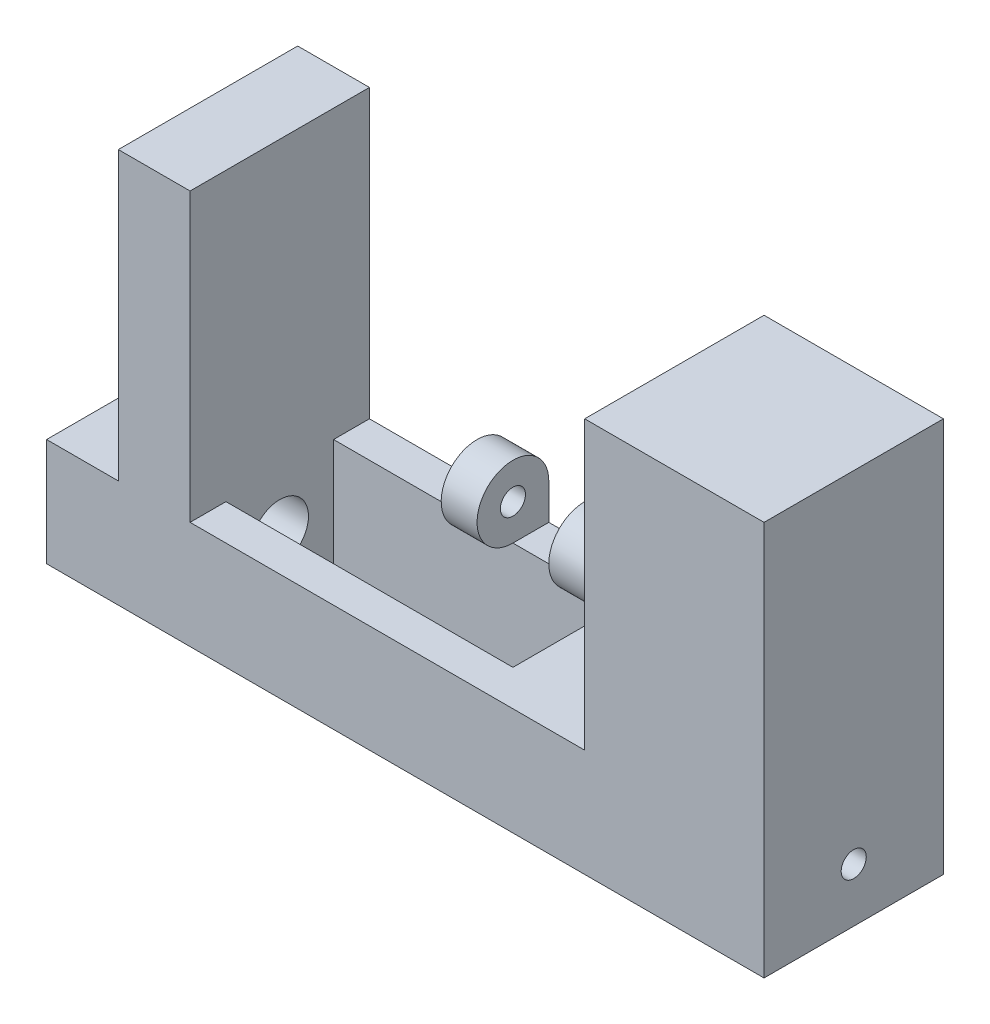
SolidWorks part; units mm, degrees
ref_plane "Front Plane" through (0, 0, 0) normal (0, 0, 1) x (1, 0, 0)
ref_plane "Top Plane" through (0, 0, 0) normal (0, 1, 0) x (1, 0, 0)
ref_plane "Right Plane" through (0, 0, 0) normal (1, 0, 0) x (0, 0, -1)
sketch "Sketch2" plane through (0, 0, 0) normal (0, 1, 0) x (1, 0, 0)
  line L1 (-20, -7.5) -> (20, -7.5)
  line L2 (-20, -7.5) -> (-20, 7.5)
  line L3 (-20, 7.5) -> (20, 7.5)
  line L4 (20, -7.5) -> (20, 7.5)
  line L5 (-20, -7.5) -> (20, 7.5) construction
  line L6 (-20, 7.5) -> (20, -7.5) construction
  line L7 (-40, -12.5) -> (60, -12.5)
  line L8 (-40, -12.5) -> (-40, 12.5)
  line L9 (-40, 12.5) -> (60, 12.5)
  line L10 (60, -12.5) -> (60, 12.5)
  point P0 (0, 0)
  point P10 (-40, 0)
  dimension "D1" = 15
  dimension "D2" = 25
  dimension "D3" = 20
  dimension "D4" = 40
  dimension "D5" = 40
extrude "Boss-Extrude1" add sketch "Sketch2" along normal blind 15
sketch "Sketch3" plane through (60, 0, 0) normal (1, 0, 0) x (0, 0, -1)
  line L0 (0, 0) -> (0, 7.5) construction
  line L1 (-12.5, 0) -> (12.5, 0) construction
  circle A0 centre (0, 7.5) radius 1.75
  dimension "D1" = 3.5
  dimension "D2" = 7.5
extrude "Cut-Extrude1" cut sketch "Sketch3" against normal up to next
sketch "Sketch4" plane through (-40, 0, 0) normal (-1, 0, 0) x (0, 0, 1)
  circle A0 centre (0, 7.5) radius 4
  point P2 (-1.0899, 7.4204)
  dimension "D2" = 8
  dimension "D1" = 7.5
extrude "Cut-Extrude2" cut sketch "Sketch4" against normal up to next
sketch "Sketch7" plane through (0, 15, 0) normal (0, 1, 0) x (1, 0, 0)
  line L0 (-40, 12.5) -> (-40, -12.5) construction
  point P0 (-35, 0)
  point P5 (0, 0)
  dimension "D1" = 5
hole_wizard "Ø3.2 (3.2) Diameter Hole1" positions "Sketch7" profile "Sketch6" hole size "Ø3.2" standard "ANSI Metric" end condition through all
sketch "Sketch6" plane through (-35, 15, 0) normal (1, 0, 0) x (0, 0, 1)
  line L0 (0, 0) -> (0, 15)
  line L1 (0, 15) -> (1.6, 15)
  line L2 (1.6, 15) -> (1.6, 0.025)
  line L3 (1.6, 0.025) -> (1.625, 0)
  line L5 (1.625, 0) -> (0, 0)
  line L6 (-1.6, 0.025) -> (-1.625, 0) construction
  line L11 (0, -6.35) -> (0, 107.95) construction
  dimension "Thru Hole Dia." = 3.2
  dimension "Thru Hole Depth" = 15
  dimension "Near C'Sink Dia." = 3.25
  dimension "Near C'Sink Angle" = 90
sketch "Sketch8" plane through (0, 15, 0) normal (0, 1, 0) x (1, 0, 0)
  line L0 (60, 12.5) -> (-40, 12.5) construction
  line L1 (-30, 12.5) -> (-20, 12.5)
  line L2 (-30, 12.5) -> (-30, -12.5)
  line L3 (-30, -12.5) -> (-20, -12.5)
  line L4 (-20, 12.5) -> (-20, -12.5)
  line L5 (-40, -12.5) -> (60, -12.5) construction
  line L6 (-20, 7.5) -> (-20, -7.5) construction
  line L7 (60, 12.5) -> (35, 12.5)
  line L8 (60, 12.5) -> (60, -12.5)
  line L9 (60, -12.5) -> (35, -12.5)
  line L10 (35, 12.5) -> (35, -12.5)
  dimension "D1" = 25
  dimension "D2" = 10
extrude "Boss-Extrude2" add sketch "Sketch8" along normal blind 40
sketch "Sketch9" plane through (-20, 0, 0) normal (1, 0, 0) x (0, 0, -1)
  line L0 (7.5, 15) -> (12.5, 15) construction
  line L1 (12.5, 55) -> (12.5, 15) construction
  line L2 (12.5, 20) -> (12.5, 15)
  line L3 (12.5, 15) -> (7.5, 15)
  circle A0 centre (7.5, 20) radius 1.75
  arc A1 (12.5, 20) -> (7.5, 15) centre (7.5, 20) ccw
  point P7 (0, 0)
  point P13 (7.5, 15)
  dimension "D1" = 3.5
  dimension "D2" = 5
  dimension "D3" = 5
extrude "Boss-Extrude3" add sketch "Sketch9" along normal blind 40
sketch "Sketch10" plane through (0, 15, 0) normal (0, 1, 0) x (1, 0, 0)
  line L0 (-20, 2.5) -> (20, 2.5) construction
  line L1 (-20, 12.5) -> (0, 12.5)
  line L2 (-20, 12.5) -> (-20, 2.5)
  line L3 (-20, 2.5) -> (0, 2.5)
  line L4 (0, 12.5) -> (0, 2.5)
  line L5 (20, 12.5) -> (-20, 12.5) construction
  line L6 (5, 12.5) -> (15, 12.5)
  line L7 (5, 12.5) -> (5, 2.5)
  line L8 (5, 2.5) -> (15, 2.5)
  line L9 (15, 12.5) -> (15, 2.5)
  line L10 (20, 2.5) -> (20, 12.5) construction
  dimension "D1" = 5
  dimension "D2" = 10
  dimension "D3" = 5
extrude "Cut-Extrude3" cut sketch "Sketch10" along normal up to next
